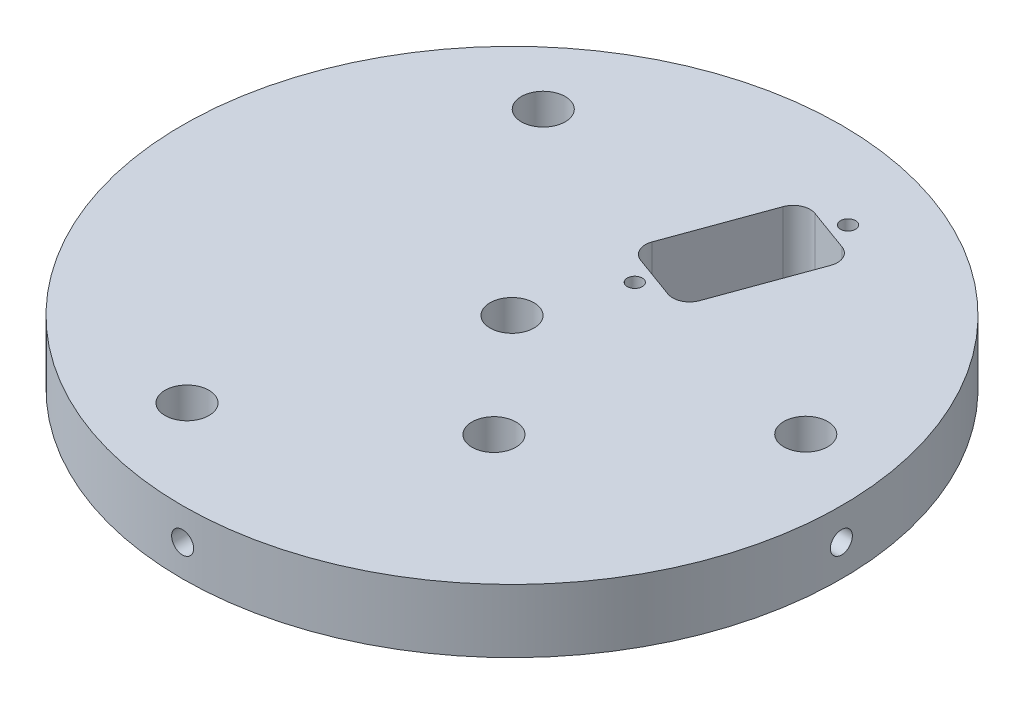
SolidWorks part; units mm, degrees
material "6061-T6 (SS)"
ref_plane "Front Plane" through (0, 0, 0) normal (0, 0, 1) x (1, 0, 0)
ref_plane "Top Plane" through (0, 0, 0) normal (0, 1, 0) x (1, 0, 0)
ref_plane "Right Plane" through (0, 0, 0) normal (1, 0, 0) x (0, 0, -1)
sketch "Sketch1" plane through (0, 0, 0) normal (0, 1, 0) x (1, 0, 0)
  line L0 (0, 0) -> (-50.3682, 60.0265)
  line L1 (0, 0) -> (50.3682, 60.0265)
  line L2 (0, 0) -> (0, 72.1431) construction
  circle A0 centre (0, 0) radius 78.359
  circle A1 centre (0, 0) radius 51.1048
  circle A2 centre (0, 0) radius 76.1746
  dimension "D1" = 156.718
  dimension "D2" = 102.2096
  dimension "D3" = 152.3492
  dimension "D4" = 80
extrude "Boss-Extrude1" add sketch "Sketch1" along normal blind 25.4 contours L2 A2 L1 A0 | L2 A1 L1 A2 | L2 A2 L1 A1 | L2 A0 L1 A2 | A2 L2 A1 L0 | A0 L2 A2 L0 | A2 L2 A0 L0 | A1 L2 A2 L0 region at (-22.4568, 0, 48.1587) region at (-40.1048, 0, -49.4238) region at (-33.0764, 0, 70.9325) region at (-48.8794, 0, -59.85)
ref_plane "Plane1" through (0, 12.7, 0) normal (0, 1, 0) x (1, 0, 0)
sketch "Sketch6" plane through (0, 25.4, 0) normal (0, 1, 0) x (1, 0, 0)
  circle A0 centre (0, 0) radius 49.5173
  dimension "D1" = 99.0346
extrude "Boss-Extrude5" add sketch "Sketch6" along normal blind 9.525
sketch "Sketch7" plane through (0, 0, 0) normal (0, -1, 0) x (1, 0, 0)
  circle A0 centre (0, 0) radius 49.5173
  dimension "D1" = 99.0346
extrude "Boss-Extrude6" add sketch "Sketch7" along normal blind 9.525
sketch "Sketch8" plane through (0, -9.525, 0) normal (0, -1, 0) x (1, 0, 0)
  circle A0 centre (0, 0) radius 46.99
  dimension "D1" = 93.98
ref_plane "Plane2" through (0, 0, -49.5173) normal (0, 0, -1) x (-1, 0, 0)
ref_plane "Plane5" through (0, 25.4, 0) normal (0, 1, 0) x (1, 0, 0)
ref_axis "Axis1" through (0, 0, 0) along (0, 1, 0)
ref_plane "Plane3" through (0, 34.925, 0) normal (0, 1, 0) x (1, 0, 0)
sketch "Sketch9" plane through (0, 34.925, 0) normal (0, 1, 0) x (1, 0, 0)
  line L0 (0, 0) -> (-26.8004, -73.6334) construction
  line L1 (0, 0) -> (32.0596, -38.2071) construction
  line L2 (0, 0) -> (0, -86.0416) construction
  circle A0 centre (0, 0) radius 3.3
  circle A1 centre (-13.031, -35.8023) radius 3.3
  circle A4 centre (14.1499, -16.8632) radius 3.3
  circle A5 centre (-24.4902, 29.1863) radius 3.3
  circle A6 centre (37.5212, 6.616) radius 3.3
  point P15 (-1.3039, -1.0954)
  point P18 (0, 0)
  dimension "D1" = 6.6
  dimension "D2" = 6.6
  dimension "D6" = 6.6
  dimension "D3" = 38.1
  dimension "D4" = 60
  dimension "D7" = 22.0133
  dimension "D8" = 20
extrude "Cut-Extrude6" cut sketch "Sketch9" against normal through all
sketch "Sketch10" plane through (0, 25.4, 0) normal (0, 1, 0) x (1, 0, 0)
  circle A0 centre (0, 0) radius 82.3228
extrude "Cut-Extrude7" cut sketch "Sketch10" against normal through all
hole_wizard "Tap Drill for #4-40 Tap1" positions "Sketch12" profile "Sketch13" hole size "#4-40" standard "ANSI Inch" end condition through all
sketch "Sketch12" plane through (0, 34.925, 0) normal (0, 1, 0) x (1, 0, 0)
  line L0 (0, 0) -> (18.6243, 51.1699) construction
  line L2 (0, 0) -> (-24.4902, 29.1863) construction
  circle A0 centre (0, 0) radius 14.3933 construction
  point P0 (4.9228, 13.5253)
  point P2 (13.4733, 37.0176)
  dimension "D3" = 28.7867
  dimension "D1" = 60
  dimension "D2" = 25
sketch "Sketch13" plane through (4.9228, 34.925, -13.5253) normal (1, 0, 0) x (0, 0, 1)
  line L0 (0, 0) -> (0, 9.525)
  line L1 (0, 9.525) -> (1.1303, 9.525)
  line L2 (1.1303, 9.525) -> (1.1303, 0)
  line L5 (1.1303, 0) -> (0, 0)
  line L11 (0, -6.35) -> (0, 107.95) construction
  dimension "Thru Hole Dia." = 2.2606
  dimension "Thru Hole Depth" = 9.525
sketch "Sketch14" plane through (0, 34.925, 0) normal (0, 1, 0) x (1, 0, 0)
  line L0 (4.9228, 13.5253) -> (13.4733, 37.0176) construction
  line L1 (12.1824, 16.0187) -> (17.4317, 30.4411)
  line L2 (8.9269, 14.5007) -> (2.4825, 16.8462)
  line L3 (15.9137, 33.6967) -> (9.4692, 36.0423)
  line L4 (0.9644, 20.1018) -> (6.2137, 34.5242)
  arc A0 (17.4317, 30.4411) -> (15.9137, 33.6967) centre (15.0449, 31.3099) ccw
  arc A1 (9.4692, 36.0423) -> (6.2137, 34.5242) centre (8.6005, 33.6555) ccw
  arc A2 (8.9269, 14.5007) -> (12.1824, 16.0187) centre (9.7956, 16.8875) ccw
  arc A3 (2.4825, 16.8462) -> (0.9644, 20.1018) centre (3.3512, 19.2331) cw
  point P0 (5.7047, 15.6734)
  dimension "D4" = 2.54
  dimension "D5" = 2.54
  dimension "D2" = 2.286
  dimension "D3" = 11.938
extrude "Cut-Extrude9" cut sketch "Sketch14" against normal through all
ref_plane "Plane6" through (49.5173, 0, 0) normal (1, 0, 0) x (0, 0, -1)
hole_wizard "Tap Drill for M4x0.7 Tap1" positions "Sketch16" profile "Sketch17" hole size "M4x0.7" standard "ANSI Metric"
sketch "Sketch16" plane through (49.5173, 0, 0) normal (1, 0, 0) x (0, 0, -1)
  line L1 (49.5173, 34.925) -> (-49.5173, 34.925) construction
  point P0 (0, 30.1625)
  dimension "D1" = 4.7625
sketch "Sketch17" plane through (49.5173, 30.1625, 0) normal (0, 1, 0) x (0, 0, -1)
  line L0 (0, 0) -> (0, 10.6434)
  line L1 (0, 10.6434) -> (1.65, 9.652)
  line L2 (1.65, 9.652) -> (1.65, 0)
  line L5 (1.65, 0) -> (0, 0)
  line L10 (0, 10.6434) -> (-1.65, 9.652) construction
  line L11 (0, -6.35) -> (0, 107.95) construction
  dimension "Hole Dia." = 3.3
  dimension "Hole Depth" = 9.652
  dimension "Drill Angle" = 118
pattern_circular "CirPattern1" count 4 over 360 about axis through (0, 34.925, 0) along (0, 1, 0) of "Tap Drill for M4x0.7 Tap1"
equation "\"AB_Coupler_OD_Length\"= 1in"
equation "\"AB_Coupling_Section_Length\"= 0.375in"
equation "\"AB_Coupler_Length\"= \"AB_Coupler_OD_Length\" + \"AB_Coupling_Section_Length\" * 2"
equation "\"Cutout_Angle\"= 60"
equation "\"AB_Coupler_Num_Screws\"= 4"
equation "\"Num_Cutouts\"= 4"
equation "\"AB_Coupler_OD\"= 4.024in"
equation "\"AB_Coupler_ID\"= 3.7in"
equation "\"AB_Coupler_Surface_Diameter\"= 3.899in"
equation "\"D2@Sketch1\"= \"Body_Tube_OD\""
equation "\"AB_Coupling_Screw_Diameter\"= 0.1065in"
equation "\"Aft_Section_Length\"= 30in"
equation "\"Mid_Coupler_Length\"= 12in"
equation "\"Lead_Screw_Dist\"= 2in"
equation "\"Lead_Screw_Diam\"= 0.375in"
equation "\"Lead_Screw_Length\"= \"Mid_Coupler_Length\" + 2*0.375in + 2*0.5in"
equation "\"Paddle_Pin_Offset\"= 0.25in"
equation "\"Paddle_Pin_Radius\"= 2.25*2/3in"
equation "\"D1@Sketch6\"=\"AB_Coupler_Surface_Diameter\""
equation "\"D1@Boss-Extrude5\"=\"AB_Coupling_Section_Length\""
equation "\"D1@Sketch7\"=\"AB_Coupler_Surface_Diameter\""
equation "\"D1@Boss-Extrude6\"=\"AB_Coupling_Section_Length\""
equation "\"D1@Sketch8\"=\"AB_Coupler_ID\""
equation "\"D3@Sketch9\"=\"Paddle_Pin_Radius\""
equation "\"Motor_OD\"= 54mm"
equation "\"AB_Paddle_Height\"= 0.375in"
equation "\"AB_Central_Bushing_Length\"= 0.75in"
equation "\"Paddle_Gear_OD\"= 3.2in"
equation "\"Fwd_BKHD_From_Top\"= 18in"
equation "\"Fin_Thickness\"= 0.118in"
equation "\"DB9_Hole_Dist\"= 25mm"
equation "\"D2@Sketch12\"=\"DB9_Hole_Dist\""
equation "\"Drive_Gear_OD\"= 1.7*2/3in"
equation "\"D3@Sketch12\"=\"Drive_Gear_OD\""
equation "\"DB9_Relief_Width\"= 0.47in"
equation "\"D3@Sketch14\"=\"DB9_Relief_Width\""
equation "\"DB9_Relief_Hole_Offset\"= 0.09in"
equation "\"D2@Sketch14\"=\"DB9_Relief_Hole_Offset\""
equation "\"D1@Sketch14\"=\"DB9_Relief_Hole_Offset\""
equation "\"Airbrakes_Wire_Hole_Dia\"= 0.25in"
equation "\"Airbrakes_Wire_Hole_Dist\"= 1.1in"
equation "\"Servo_Gear_Offset\"= 0.5in"
equation "\"Motor_Length\"= 401mm"
equation "\"Body_Tube_OD\"= 4.024in"
equation "\"Body_Tube_ID\"= 3.90in"
equation "\"Coupler_OD\"= 3.899in"
equation "\"Coupler_ID\"= 3.755in"
equation "\"Fwd_Section_Length\"= 25in"
equation "\"Mid_Section_Length\"= 6in"
equation "\"Aft_Upper_Tube_Length\"= 10in"
equation "\"Aft_Lower_Tube_Length\"= 18in"
equation "\"Nosecone_Coupler_Length\"= 5in"
equation "\"Avionics_Bulkhead_Thickness\"= 0.25in"
equation "\"Avionics_Bulkhead_Lip\"= 0.125in"
equation "\"Avionics_Board_Length\"= \"Mid_Coupler_Length\" - 2*\"Avionics_Bulkhead_Lip\""
equation "\"Lead_Screw_Hole_Diam\"= (27/64)*1in"
equation "\"Centering_Ring_Cutout_Dia\"=1.5in"
equation "\"D7@Sketch9\"=\"Drive_Gear_OD\"/2+.3"
equation "\"D1@Sketch16\"=.375/2"
